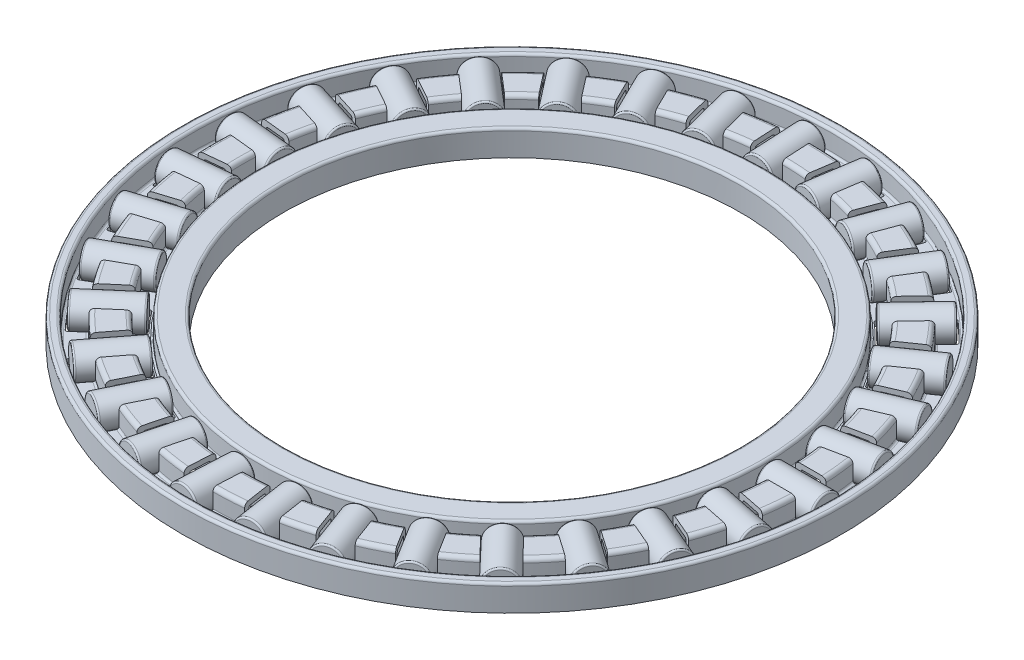
SolidWorks part; units mm, degrees
note: '?' marks a value the reader was unsure of.
material "AISI 304"
ref_plane "Front Plane" through (0, 0, 0) normal (0, 0, 1) x (1, 0, 0)
ref_plane "Top Plane" through (0, 0, 0) normal (0, 1, 0) x (1, 0, 0)
ref_plane "Right Plane" through (0, 0, 0) normal (1, 0, 0) x (0, 0, -1)
sketch "Sketch1" plane through (0, 0, 0) normal (1, 0, 0) x (0, 0, -1)
  line L0 (-32.5, 0) -> (32.5, 0) construction
  line L1 (-22.525, 0) -> (22.525, 0) construction
  line L2 (32.5, -1.5) -> (32.5, 1.5) construction
  line L3 (22.525, -1.275) -> (22.525, 1.275) construction
  line L4 (22.525, -1.275) -> (23.35, -1.275) construction
  line L5 (23.35, -1.275) -> (23.35, 0.7792) construction
  line L6 (23.35, 0.7792) -> (24.175, 0.7792) construction
  line L7 (24.175, 0.7792) -> (24.175, -1.275) construction
  line L8 (24.175, -1.275) -> (27.0042, -1.275) construction
  line L9 (27.0042, -1.275) -> (27.0042, 0.7792) construction
  line L10 (27.0042, 0.7792) -> (29.0042, 0.7792) construction
  line L11 (29.0042, 0.7792) -> (29.0042, -1.275) construction
  line L12 (29.0042, -1.275) -> (31.8333, -1.275) construction
  line L13 (31.8333, -1.275) -> (31.8333, 0.7792) construction
  line L14 (31.8333, 0.7792) -> (32.1667, 0.7792) construction
  line L15 (22.525, 1.275) -> (25, 1.275) construction
  line L16 (25, 1.275) -> (25, -0.7792) construction
  line L17 (25, -0.7792) -> (26.5083, -0.7792) construction
  line L18 (26.5083, -0.7792) -> (26.5083, 1.275) construction
  line L19 (26.5083, 1.275) -> (29.5, 1.275) construction
  line L20 (29.5, 1.275) -> (29.5, -0.7792) construction
  line L21 (29.5, -0.7792) -> (31.5, -0.7792) construction
  line L22 (31.5, -0.7792) -> (31.5, 1.275) construction
  line L23 (31.5, 1.275) -> (32.5, 1.275) construction
  line L24 (27.0042, 0.7792) -> (26.5083, 0.7792) construction
  line L25 (24.175, 0.7792) -> (24.175, 1.275) construction
  line L26 (29.0042, 0.7792) -> (29.5, 0.7792) construction
  line L27 (25, -0.7792) -> (25, -1.275) construction
  line L28 (25, -0.7792) -> (24.175, -0.7792) construction
  line L29 (31.8333, 0.7792) -> (31.5, 0.7792) construction
  line L30 (32.1667, 0.7792) -> (32.1667, -1.275) construction
  line L31 (32.1667, -1.275) -> (32.5, -1.275) construction
  line L32 (0, 1.5) -> (0, -1.5) construction
  line L33 (-25, 1.5) -> (25, 1.5) construction
  line L34 (-31.5, 1.275) -> (31.5, 1.275) construction
  line L35 (32.1667, 0.7792) -> (32.5, 0.7792) construction
  line L36 (26.5083, -0.7792) -> (26.5083, -1.275) construction
  line L37 (29.0042, 0.7792) -> (29.0042, 1.275) construction
  line L38 (23.35, -0.7792) -> (22.525, -0.7792) construction
  line L39 (24.175, -0.7792) -> (23.35, -0.7792) construction
  point P4 (0, 0)
  point P8 (0, 0)
  point P11 (32.5, 0)
  point P14 (22.525, 0)
  point P45 (0, 1.5)
  point P48 (0, 0)
  point P49 (0, 1.5)
  point P55 (0, 1.275)
  dimension "OD" = 65
  dimension "ID" = 45.05
  dimension "Thickness" = 3
  dimension "Approx. Raceway Thickness" = 2.55
  dimension "Inner Raceway" = 50
  dimension "Outer Raceway" = 63
  dimension "Approx. Raceway Notch Width" = 2
  dimension "D3" = 2
sketch "Sketch2" plane through (0, 0, 0) normal (0, 1, 0) x (1, 0, 0)
  line L0 (25, 0) -> (31.5, 0) construction
  line L1 (31.175, 0) -> (25.325, 0)
  line L2 (31.1389, -1.5) -> (25.2805, -1.5)
  line L3 (31.1389, 1.5) -> (25.2805, 1.5)
  circle A0 centre (0, 0) radius 22.525
  circle A1 centre (0, 0) radius 25
  circle A2 centre (0, 0) radius 31.5
  circle A3 centre (0, 0) radius 32.5
  arc A4 (25.2805, -1.5) -> (25.2805, 1.5) centre (0, 0) ccw
  arc A5 (31.1389, -1.5) -> (31.1389, 1.5) centre (0, 0) ccw
  arc A6 (31.1389, 1.5) -> (30.8923, 4.1889) centre (0, 0) ccw
  point P15 (28.25, 0)
  dimension "Approx. Roller Length" = 5.85
  dimension "Roller Thickness" = 3
  dimension "Roller Arc Length" = 3.0012
  dimension "Approx. Roller Gap" = 2.701
sketch "Sketch3" plane through (0, 0, 0) normal (1, 0, 0) x (0, 0, -1)
  line L0 (23.35, -1.275) -> (23.35, 0.7792)
  line L1 (23.35, 0.7792) -> (24.175, 0.7792)
  line L2 (24.175, 0.7792) -> (24.175, -1.275)
  line L3 (24.175, -1.275) -> (27.0042, -1.275)
  line L4 (27.0042, -1.275) -> (27.0042, 0.7792)
  line L5 (27.0042, 0.7792) -> (29.0042, 0.7792)
  line L6 (29.0042, 0.7792) -> (29.0042, -1.275)
  line L7 (29.0042, -1.275) -> (31.8333, -1.275)
  line L8 (31.8333, -1.275) -> (31.8333, 0.7792)
  line L9 (31.8333, 0.7792) -> (32.1667, 0.7792)
  line L10 (32.1667, 0.7792) -> (32.1667, -1.275)
  line L11 (32.1667, -1.275) -> (32.5, -1.275)
  line L12 (32.5, -1.275) -> (32.5, 1.275)
  line L13 (32.5, 1.275) -> (31.5, 1.275)
  line L14 (31.5, 1.275) -> (31.5, -0.7792)
  line L15 (31.5, -0.7792) -> (29.5, -0.7792)
  line L16 (29.5, -0.7792) -> (29.5, 1.275)
  line L17 (29.5, 1.275) -> (26.5083, 1.275)
  line L18 (26.5083, 1.275) -> (26.5083, -0.7792)
  line L19 (26.5083, -0.7792) -> (25, -0.7792)
  line L20 (25, -0.7792) -> (25, 1.275)
  line L21 (25, 1.275) -> (22.525, 1.275)
  line L22 (22.525, 1.275) -> (22.525, -1.275)
  line L23 (22.525, -1.275) -> (23.35, -1.275)
revolve "Revolve1" add sketch "Sketch3" angle 360 about L32
fillet "Fillet1" radius 0.4 4 edges at (0, -1.275, 29.0042) (0, -1.275, 31.8333) (0, -1.275, 24.175) (0, -1.275, 27.0042)
fillet "Fillet2" radius 0.4 2 edges at (0, 1.275, 29.5) (0, 1.275, 26.5083)
fillet "Fillet3" radius 0.25 4 edges at (0, 1.275, 31.5) (0, 1.275, 32.5) (0, 1.275, 25) (0, 1.275, 22.525)
fillet "Fillet4" radius 0.2 6 edges at (0, 0.7792, 27.0042) (0, 0.7792, 29.0042) (0, -0.7792, 31.5) (0, -0.7792, 29.5) (0, -0.7792, 26.5083) (0, -0.7792, 25)
sketch "Sketch4" plane through (0, 0, 0) normal (0, 1, 0) x (1, 0, 0)
  line L0 (25.2805, 1.5) -> (31.1389, 1.5)
  line L1 (25.2805, -1.5) -> (31.1389, -1.5)
  arc A0 (25.2805, -1.5) -> (25.2805, 1.5) centre (0, 0) ccw construction
  arc A1 (25.2805, -1.5) -> (25.2805, 1.5) centre (0, 0) ccw
  arc A2 (31.1389, -1.5) -> (31.1389, 1.5) centre (0, 0) ccw construction
  arc A3 (31.1389, -1.5) -> (31.1389, 1.5) centre (0, 0) ccw
extrude "Cut-Extrude1" cut sketch "Sketch4" against normal through all both and the other way through all
fillet "Fillet5" radius 0.1501 4 edges at (31.1389, -1.0271, -1.5) (31.1389, -1.0271, 1.5) (25.2805, -1.0271, -1.5) (25.2805, -1.0271, 1.5)
pattern_circular "CirPattern1" count 31 over 360 about axis through (0, 0, 0) along (0, 1, 0) of "Cut-Extrude1", "Fillet5"
sketch "Sketch5" plane through (0, 0, 0) normal (0, 1, 0) x (1, 0, 0)
  line L0 (25.4393, 0) -> (25.4393, 1.5)
  line L2 (25.4393, 1.5) -> (30.9956, 1.5)
  line L3 (30.9956, 1.5) -> (30.9956, 0)
  line L4 (30.9956, 0) -> (25.4393, 0)
  line L5 (31.175, 0) -> (25.325, 0) construction
revolve "Revolve2" add sketch "Sketch5" angle 360 about L1
fillet "Fillet6" radius 0.1501 2 edges at (25.4393, 0, -1.5) (30.9956, 0, -1.5)
pattern_circular "CirPattern2" count 31 over 360 about axis through (0, 0, 0) along (0, 1, 0) of bodies 107
ref_axis "Center Axis 1" through (0, 1.65, 0) along (0, -1, 0)?
ref_plane "Contact Plane 1" through (0, 1.5, 0) normal (0, 1, 0) x (1, 0, 0)
ref_plane "Contact Plane 2" through (0, -1.5, 0) normal (0, 1, 0) x (1, 0, 0)
equation "\"Approx. Raceway Thickness@Sketch1\" = \"Thickness@Sketch1\" * .85"
equation "\"Approx. Raceway Notch Width@Sketch1\" =  ( \"Outer Raceway@Sketch1\" - \"Inner Raceway@Sketch1\" )  / 6.5"
equation "\"D3@Sketch1\" = \"Approx. Raceway Notch Width@Sketch1\""
equation "\"D1@Fillet2\"=\"D1@Fillet1\""
equation "\"D1@Fillet3\"=(\"OD@Sketch1\"-\"Outer Raceway@Sketch1\")/8"
equation "\"D1@Fillet1\" = \"Approx. Raceway Notch Width@Sketch1\" * 2 / 10"
equation "\"D1@Fillet4\"=\"D1@Fillet2\"/2"
equation "\"Approx. Roller Length@Sketch2\" =  ( \"Outer Raceway@Sketch1\" - \"Inner Raceway@Sketch1\" )  / 2 * .9"
equation "\"Approx. Roller Gap@Sketch2\" = \"Roller Arc Length@Sketch2\" * .9"
equation "\"Raceway Diff\"= ( \"Outer Raceway@Sketch1\" - \"Inner Raceway@Sketch1\" )"
equation "\"Circumference\"= ( \"Inner Raceway@Sketch1\" + ( \"Raceway Diff\" / 2 ) ) * 3.14"
equation "\"Instances\"= int ( \"Circumference\" /  ( \"Roller Arc Length@Sketch2\" + \"Approx. Roller Gap@Sketch2\" )  ) "
equation "\"D1@CirPattern1\"=\"Instances\""
equation "\"D1@Fillet5\" = \"Roller Arc Length@Sketch2\" / 20"
equation "\"D1@Fillet6\" = \"Roller Arc Length@Sketch2\" / 20"
equation "\"D1@CirPattern2\" = \"D1@CirPattern1\""
equation "\"Roller Thickness@Sketch2\" = \"Thickness@Sketch1\""
